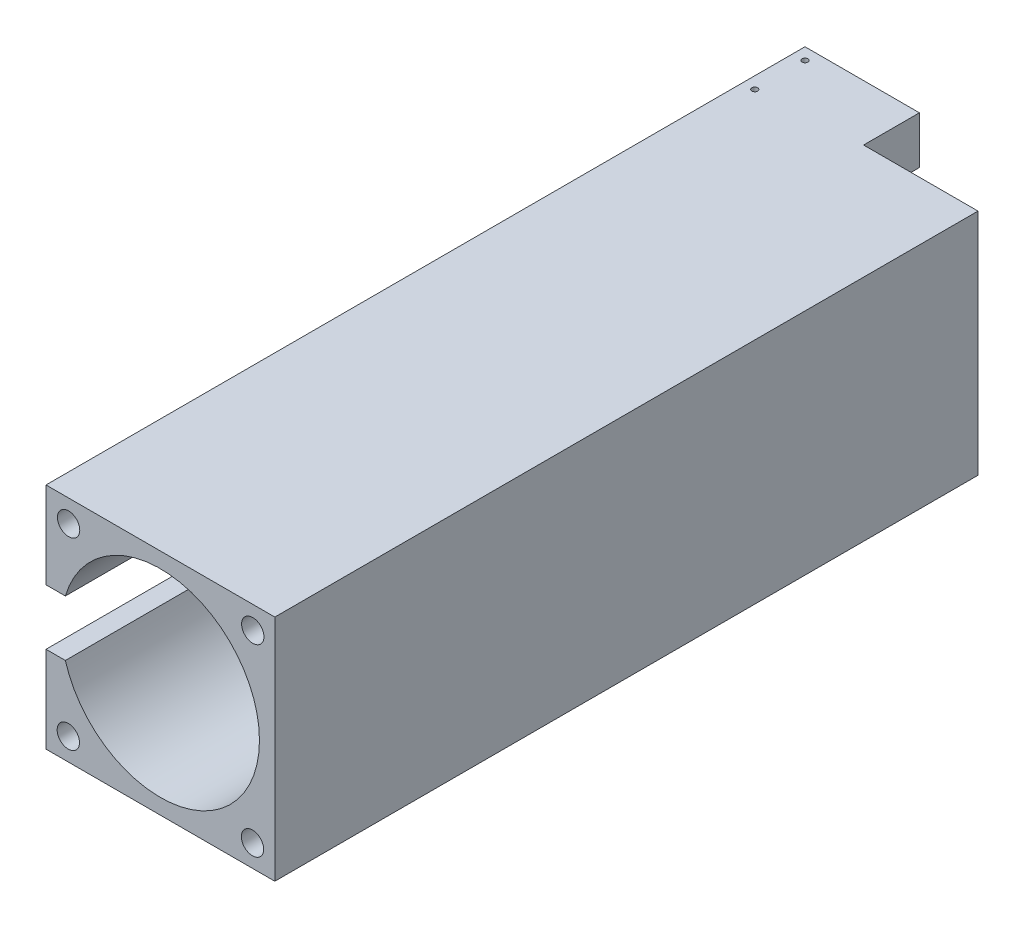
SolidWorks part; units mm, degrees
ref_plane "前基準面" through (0, 0, 0) normal (0, 0, 1) x (1, 0, 0)
ref_plane "上基準面" through (0, 0, 0) normal (0, 1, 0) x (1, 0, 0)
ref_plane "右基準面" through (0, 0, 0) normal (1, 0, 0) x (0, 0, -1)
ref_axis "基準軸1" through (0, -55, 0) along (0, 1, 0)
ref_axis "基準軸2" through (-88.99, 0, 0) along (1, 0, 0)
ref_axis "基準軸3" through (0, 0, 55) along (0, 0, -1)
sketch "草圖1" plane through (0, 0, 0) normal (0, 0, 1) x (1, 0, 0)
  line L0 (0, -55) -> (0, 55) construction
  line L1 (-41, -41) -> (41, -41)
  line L2 (-41, -41) -> (-41, 41)
  line L3 (-41, 41) -> (41, 41)
  line L4 (41, -41) -> (41, 41)
  line L5 (55, 0) -> (-55, 0) construction
  circle A0 centre (0, 0) radius 35.5
  point P7 (0, -41)
  point P10 (41, 0)
  dimension "D1" = 71
  dimension "D2" = 82
  dimension "D3" = 82
extrude "填料-伸長1" add sketch "草圖1" along normal blind 245
sketch "草圖2" plane through (0, 0, 0) normal (0, 0, -1) x (-1, 0, 0)
  line L1 (-41, 41) -> (41, 41)
  line L2 (-41, 41) -> (-41, -41)
  line L3 (-41, -41) -> (41, -41)
  line L4 (41, 41) -> (41, -41)
extrude "填料-伸長2" add sketch "草圖2" along normal blind 27
ref_plane "平面1" through (0, 0, -13.5) normal (0, 0, -1) x (-1, 0, 0)
sketch "草圖3" plane through (0, 0, 245) normal (0, 0, 1) x (1, 0, 0)
  line L0 (-41, 41) -> (-41, -41) construction
  line L1 (-41, 10) -> (-33, 10)
  line L2 (-41, 10) -> (-41, -10)
  line L3 (-41, -10) -> (-33, -10)
  line L4 (-33, 10) -> (-33, -10)
  line L6 (55, 0) -> (-55, 0) construction
  point P6 (-33, 0)
  dimension "D1" = 8
  dimension "D2" = 20
extrude "除料-伸長1" cut sketch "草圖3" against normal up to surface (245 mm away) up to face at (35.5, 0, 0)
sketch "草圖4" plane through (0, 0, 245) normal (0, 0, 1) x (1, 0, 0)
  line L1 (41, 41) -> (-41, 41) construction
  line L2 (-41, 41) -> (-41, 10) construction
  line L3 (-41, -41) -> (41, -41) construction
  line L4 (-41, -10) -> (-41, -41) construction
  circle A0 centre (-32.9, 33) radius 4
  circle A1 centre (33.1, 32.9) radius 4
  circle A2 centre (33, -33.1) radius 4
  circle A3 centre (-33, -33) radius 4
  point P15 (0.05, -0.05)
  dimension "D1" = 8
  dimension "D5" = 8
  dimension "D2" = 8
  dimension "D3" = 8.1
  dimension "D6" = 8
  dimension "D4" = 4
extrude "除料-伸長2" cut sketch "草圖4" against normal blind 20
fillet "圓角2" radius 3 1 edges at (-28.9, 33, 225)
fillet "圓角3" radius 3 1 edges at (37.1, 32.9, 225)
fillet "圓角4" radius 3 1 edges at (-29, -33, 225)
fillet "圓角5" radius 3 1 edges at (37, -33.1, 225)
sketch "草圖5" plane through (0, 41, 0) normal (0, 1, 0) x (1, 0, 0)
  line L0 (-41, -245) -> (-41, 27) construction
  line L4 (-41, 27) -> (41, 27) construction
  circle A2 centre (-36.75, 22.75) radius 1.05
  circle A3 centre (-36.75, 4.75) radius 1.05
  dimension "D1" = 18
  dimension "D2" = 2.1
  dimension "D3" = 2.1
  dimension "D4" = 4.25
  dimension "D5" = 4.25
  dimension "D6" = 4.25
extrude "除料-伸長3" cut sketch "草圖5" against normal blind 10
ref_plane "平面2" through (0, 35, 0) normal (0, 1, 0) x (1, 0, 0)
sketch "草圖6" plane through (0, 35, 0) normal (0, 1, 0) x (1, 0, 0)
  circle A0 centre (-36.75, 22.75) radius 1.05
  circle A1 centre (-36.75, 4.75) radius 1.05
  dimension "D1" = 2.1
  dimension "D2" = 2.1
extrude "填料-伸長3" add sketch "草圖6" along normal blind 0.2
sketch "草圖7" plane through (-41, 0, 0) normal (1, 0, 0) x (0, 0, -1)
  line L1 (27, -41) -> (7, -41)
  line L2 (27, -41) -> (27, 24)
  line L3 (27, 24) -> (7, 24)
  line L4 (7, -41) -> (7, 24)
  dimension "D1" = 20
  dimension "D2" = 65
extrude "除料-伸長5" cut sketch "草圖7" along normal up to next
sketch "草圖8" plane through (0, 41, 0) normal (0, 1, 0) x (1, 0, 0)
  line L0 (0, -45.1) -> (0, 45.1) construction
  line L1 (41, 27) -> (0, 27)
  line L2 (41, 27) -> (41, 7)
  line L3 (41, 7) -> (0, 7)
  line L4 (0, 27) -> (0, 7)
  dimension "D1" = 20
extrude "除料-伸長6" cut sketch "草圖8" against normal up to next
sketch "草圖9" plane through (0, 0, -7) normal (0, 0, -1) x (-1, 0, 0)
  line L0 (-41, -41) -> (-41, 41) construction
  line L1 (-41, -41) -> (41, -41) construction
  line L2 (41, 24) -> (41, -41) construction
  line L3 (0, 41) -> (-41, 41) construction
  line L4 (45.1, 0) -> (-45.1, 0) construction
  circle A0 centre (-33, 33) radius 1.2
  circle A1 centre (-33, -33) radius 1.2
  circle A2 centre (33, -33) radius 1.2
  circle A3 centre (38, 20) radius 1.2
  dimension "D1" = 2.4
  dimension "D2" = 2.4
  dimension "D3" = 2.4
  dimension "D10" = 2.4
  dimension "D4" = 8
  dimension "D5" = 8
  dimension "D6" = 8
  dimension "D7" = 8
  dimension "D8" = 8
  dimension "D9" = 8
  dimension "D11" = 3
  dimension "D12" = 20
extrude "除料-伸長7" cut sketch "草圖9" against normal blind 10
sketch "草圖10" plane through (0, 0, 0) normal (1, 0, 0) x (0, 0, -1)
  line L1 (7, 24) -> (27, 24)
  line L2 (7, 24) -> (7, 41)
  line L3 (7, 41) -> (27, 41)
  line L4 (27, 24) -> (27, 41)
